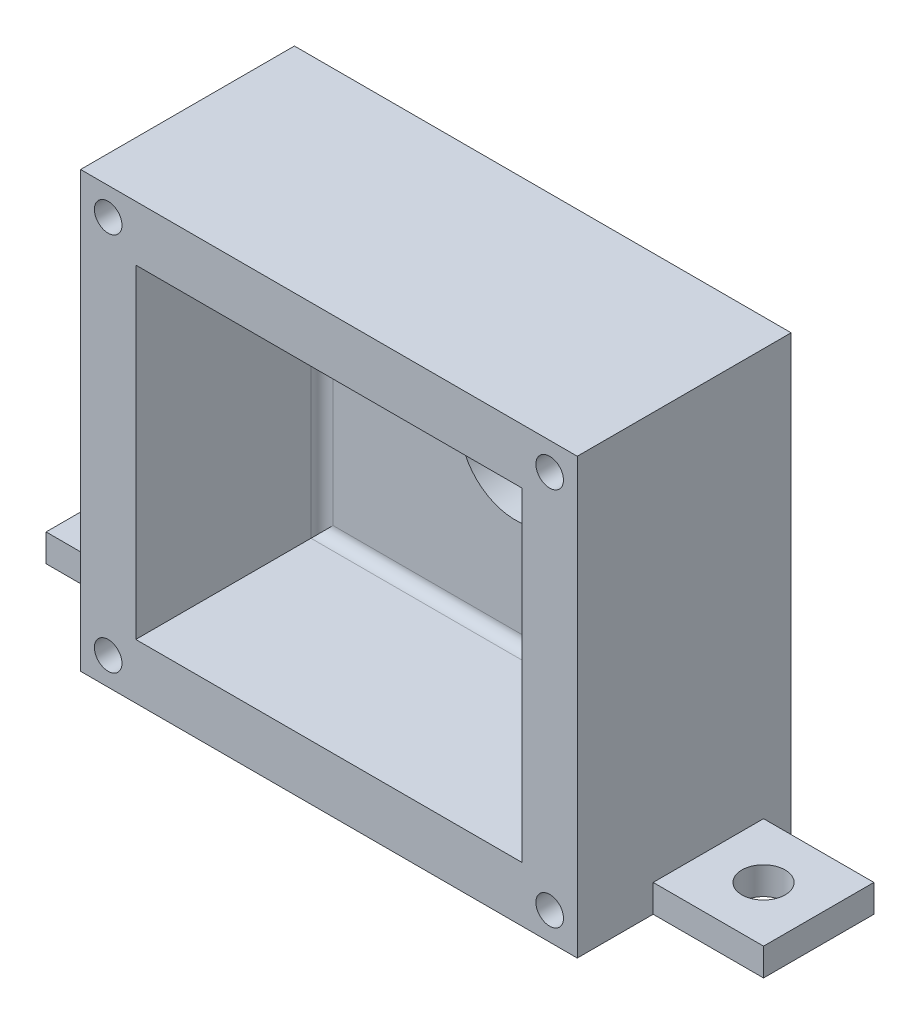
SolidWorks part; units mm, degrees
ref_plane "Front Plane" through (0, 0, 0) normal (0, 0, 1) x (1, 0, 0)
ref_plane "Top Plane" through (0, 0, 0) normal (0, 1, 0) x (1, 0, 0)
ref_plane "Right Plane" through (0, 0, 0) normal (1, 0, 0) x (0, 0, -1)
sketch "Sketch1" plane through (0, 0, 0) normal (0, 0, 1) x (1, 0, 0)
  line L1 (22.225, -18.6531) -> (-22.225, -18.6531)
  line L2 (22.225, -18.6531) -> (22.225, 18.6531)
  line L3 (22.225, 18.6531) -> (-22.225, 18.6531)
  line L4 (-22.225, -18.6531) -> (-22.225, 18.6531)
  line L5 (22.225, -18.6531) -> (-22.225, 18.6531) construction
  line L6 (22.225, 18.6531) -> (-22.225, -18.6531) construction
  line L7 (28.575, -25.0031) -> (-28.575, -25.0031)
  line L8 (28.575, -25.0031) -> (28.575, 25.0031)
  line L9 (28.575, 25.0031) -> (-28.575, 25.0031)
  line L10 (-28.575, -25.0031) -> (-28.575, 25.0031)
  line L11 (28.575, -25.0031) -> (-28.575, 25.0031) construction
  line L12 (28.575, 25.0031) -> (-28.575, -25.0031) construction
  point P0 (0, 0)
  point P6 (0, 0)
  dimension "D1" = 6.35
  dimension "D2" = 6.35
  dimension "D3" = 44.45
  dimension "D4" = 37.3062
extrude "Boss-Extrude1" add sketch "Sketch1" along normal blind 21.4312
sketch "Sketch2" plane through (0, 0, 0) normal (0, 0, 1) x (1, 0, 0)
  line L1 (28.575, -25.0031) -> (-28.575, -25.0031)
  line L2 (28.575, -25.0031) -> (28.575, 25.0031)
  line L3 (28.575, 25.0031) -> (-28.575, 25.0031)
  line L4 (-28.575, -25.0031) -> (-28.575, 25.0031)
  line L5 (28.575, -25.0031) -> (-28.575, 25.0031) construction
  line L6 (28.575, 25.0031) -> (-28.575, -25.0031) construction
  circle A0 centre (0, 0) radius 6.35
  point P0 (0, 0)
  dimension "D1" = 12.7
extrude "Boss-Extrude2" add sketch "Sketch2" against normal blind 3.175
sketch "Sketch4" plane through (0, 0, 0) normal (0, 0, 1) x (1, 0, 0)
  line L1 (-28.575, -25.0031) -> (-41.275, -25.0031)
  line L2 (-28.575, -25.0031) -> (-28.575, -21.8281)
  line L3 (-28.575, -21.8281) -> (-41.275, -21.8281)
  line L4 (-41.275, -25.0031) -> (-41.275, -21.8281)
  line L5 (28.575, -25.0031) -> (41.275, -25.0031)
  line L6 (28.575, -25.0031) -> (28.575, -21.8281)
  line L7 (28.575, -21.8281) -> (41.275, -21.8281)
  line L8 (41.275, -25.0031) -> (41.275, -21.8281)
  dimension "D1" = 3.175
  dimension "D2" = 12.7
extrude "Boss-Extrude3" add sketch "Sketch4" along direction (0, 0, 1) on the side of the normal blind 12.7
sketch "Sketch5" plane through (0, -21.8281, 0) normal (0, 1, 0) x (1, 0, 0)
  line L0 (-41.275, 0) -> (-28.575, -12.7) construction
  line L1 (-28.575, -12.7) -> (-28.575, 0) construction
  line L2 (-28.575, 0) -> (-41.275, -12.7) construction
  line L3 (28.575, 0) -> (41.275, -12.7) construction
  line L4 (41.275, 0) -> (28.575, -12.7) construction
  circle A0 centre (-34.925, -6.35) radius 2.4892
  circle A1 centre (34.925, -6.35) radius 2.4892
  point P16 (-34.925, -6.35)
  point P17 (34.925, -6.35)
  dimension "D1" = 4.9784
  dimension "D2" = 4.9784
extrude "Cut-Extrude1" cut sketch "Sketch5" against normal blind 3.175
fillet "Fillet1" radius 1.27 4 edges at (0, -18.6531, 0) (22.225, 0, 0) (0, 18.6531, 0) (-22.225, 0, 0)
sketch "Sketch6" plane through (0, 0, 21.4312) normal (0, 0, 1) x (1, 0, 0)
  line L0 (-28.575, 21.8281) -> (28.575, 21.8281) construction
  line L1 (-28.575, 25.0031) -> (-28.575, -25.0031) construction
  line L2 (28.575, -25.0031) -> (28.575, 25.0031) construction
  line L3 (26.9875, -21.8281) -> (-26.9875, -21.8281) construction
  line L6 (28.575, 25.0031) -> (-28.575, 25.0031) construction
  line L7 (25.4, 21.8281) -> (25.4, -21.8281) construction
  line L8 (25.4, -21.8281) -> (24.196, -20.7934) construction
  line L9 (-25.4, 21.8281) -> (-25.4, -21.8281) construction
  line L10 (-28.575, -25.0031) -> (28.575, -25.0031) construction
  line L11 (-24.196, 20.7934) -> (-25.4, 21.8281) construction
  circle A0 centre (-25.4, 21.8281) radius 1.5875
  circle A1 centre (25.4, 21.8281) radius 1.5875
  circle A2 centre (25.4, -21.8281) radius 1.5875
  circle A3 centre (-25.4, -21.8281) radius 1.5875
  dimension "D2" = 3.175
  dimension "D4" = 3.175
  dimension "D1" = 3.175
  dimension "D3" = 3.175
  dimension "D5" = 3.175
extrude "Cut-Extrude2" cut sketch "Sketch6" against normal blind 9.525
